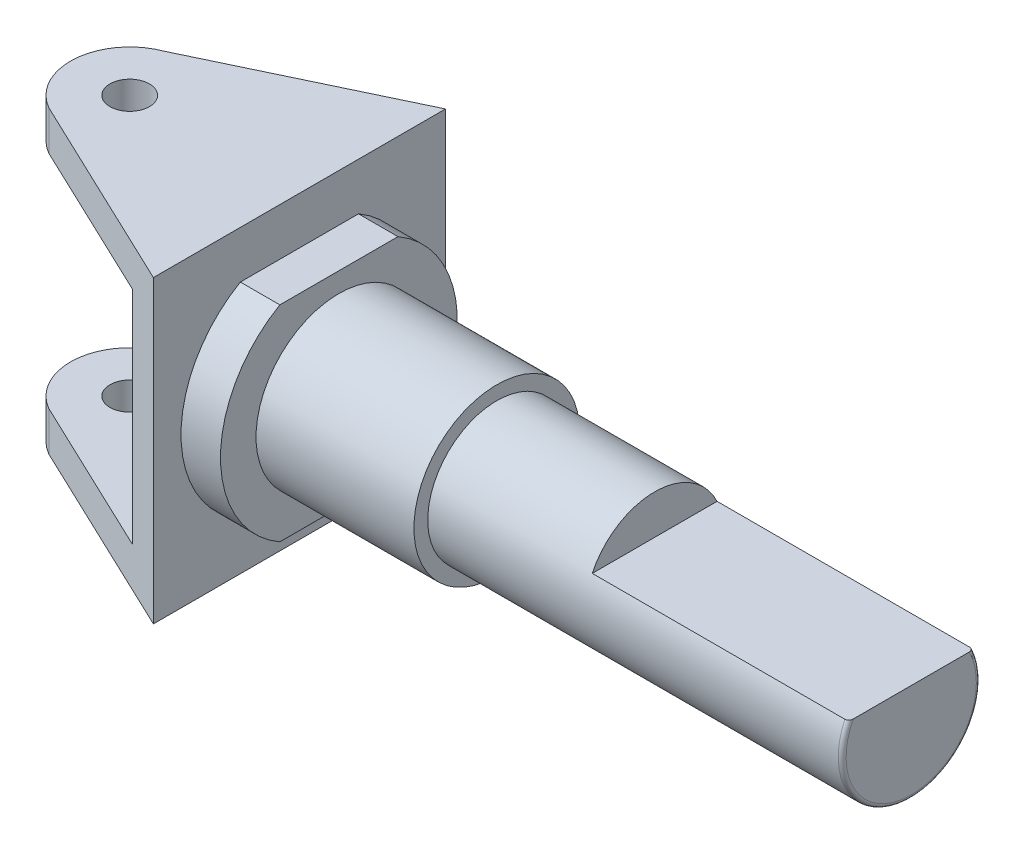
SolidWorks part; units mm, degrees
ref_plane "Front Plane" through (0, 0, 0) normal (0, 0, 1) x (1, 0, 0)
ref_plane "Top Plane" through (0, 0, 0) normal (0, 1, 0) x (1, 0, 0)
ref_plane "Right Plane" through (0, 0, 0) normal (1, 0, 0) x (0, 0, -1)
sketch "Sketch1" plane through (0, 0, 0) normal (0, 0, 1) x (1, 0, 0)
  line L0 (-61.9499, 30.1039) -> (-61.9499, 20.1039)
  line L5 (-61.9499, 30.1039) -> (-3.9499, 30.1039)
  line L6 (-3.9499, 30.1039) -> (-3.9499, -45.8961)
  line L7 (-3.9499, -45.8961) -> (-61.9499, -45.8961)
  line L8 (-61.9499, -45.8961) -> (-61.9499, -35.8961)
  line L9 (-61.9499, -35.8961) -> (-13.9499, -35.8961)
  line L10 (-13.9499, -35.8961) -> (-13.9499, 20.1039)
  line L11 (-61.9499, 20.1039) -> (-13.9499, 20.1039)
extrude "Boss-Extrude1" add sketch "Sketch1" along normal blind 74
sketch "Sketch2" plane through (0, 30.1039, 0) normal (0, 1, 0) x (1, 0, 0)
  line L0 (-3.9499, -74) -> (-54.4721, -49.9775)
  line L2 (-3.9499, 0) -> (-52.2674, -22.9741)
  line L4 (-3.9499, 0) -> (-61.9499, 0)
  line L5 (-61.9499, 0) -> (-61.9499, -37)
  line L6 (-3.9499, -74) -> (-61.9499, -74)
  line L7 (-61.9499, -74) -> (-61.9499, -37)
  arc A1 (-52.2674, -22.9741) -> (-54.4721, -49.9775) centre (-46.9499, -37) ccw
  line M2 (-3.9499, 0) -> (-61.9499, 0)
  line M3 (-61.9499, 0) -> (-61.9499, -74)
  line M4 (-61.9499, -74) -> (-3.9499, -74)
extrude "Cut-Extrude1" cut sketch "Sketch2" against normal blind 100 contours A1 L2 M2 M3 | A1 L0 M3 M4 region at (-42.9391, 30.1039, 64.4486) region at (-42.9381, 30.1039, 9.55)
sketch "Sketch3" plane through (0, 30.1039, 0) normal (0, 1, 0) x (1, 0, 0)
  circle A0 centre (-46.9499, -37) radius 5
extrude "Cut-Extrude2" cut sketch "Sketch3" against normal blind 100
sketch3d "3DSketch4"
  line L0 (-8.9499, 30.1039, 74) -> (-8.9499, -7.8961, 74) construction
  line L1 (-8.9499, -7.8961, 74) -> (-8.9499, -7.8961, 0) construction
  circle A0 centre (-8.9499, -7.8961, 37) radius 30
  point P5 (21.0501, -7.8961, 37)
  dimension "D1" = 5
extrude "Boss-Extrude2" add sketch "3DSketch4" along direction (1, 0, 0) on the side of the normal blind 15
sketch3d "3DSketch5"
  line L0 (1.0501, 30.1039, 74) -> (1.0501, -45.8961, 74) construction
  line L1 (1.0501, -7.8961, 74) -> (1.0501, -7.8961, 0) construction
  circle A4 centre (1.0501, -7.8961, 37) radius 21
  point P2 (22.0501, -7.8961, 37)
  dimension "D2" = 42
  dimension "D1" = 5
extrude "Boss-Extrude3" add sketch "3DSketch5" along direction (1, 0, 0) on the side of the normal blind 45
sketch3d "3DSketch6"
  line L0 (41.0501, -45.8961, 74) -> (41.0501, -7.8961, 74) construction
  line L1 (41.0501, -7.8961, 74) -> (41.0501, -7.8961, 0) construction
  circle A0 centre (41.0501, -7.8961, 37) radius 17.5
  point P6 (58.5501, -7.8961, 37)
  dimension "D1" = 5
extrude "Boss-Extrude4" add sketch "3DSketch6" along direction (1, 0, 0) on the side of the normal blind 110
fillet "Fillet1" radius 1 1 edges at (151.0501, -7.8961, 19.5)
sketch "Sketch4" plane through (151.0501, 0, 0) normal (1, 0, 0) x (0, 0, -1)
  line L1 (-52.8114, -0.3961) -> (-21.1886, -0.3961) construction
  line L2 (-52.8114, -0.3961) -> (-21.1886, -0.3961)
  arc A1 (-21.1886, -0.3961) -> (-52.8114, -0.3961) centre (-37, -7.8961) ccw
extrude "Cut-Extrude3" cut sketch "Sketch4" against normal blind 65
sketch "Sketch5" plane through (6.0501, 0, 0) normal (1, 0, 0) x (0, 0, -1)
  line L0 (-37, -7.8961) -> (-37, 18.1039) construction
  line L3 (-37, -7.8961) -> (-37, -33.8961) construction
  line L4 (-37, 18.1039) -> (-22.0334, 18.1039) construction
  line L5 (-22.0334, 18.1039) -> (-51.9666, 18.1039)
  line L6 (-37, -33.8961) -> (-51.9666, -33.8961) construction
  line L7 (-51.9666, -33.8961) -> (-22.0334, -33.8961)
  arc A0 (-51.9666, -33.8961) -> (-22.0334, -33.8961) centre (-37, -7.8961) ccw
  arc A1 (-22.0334, 18.1039) -> (-51.9666, 18.1039) centre (-37, -7.8961) ccw
  circle A2 centre (-37, -7.8961) radius 30 construction
  circle A3 centre (-37, -7.8961) radius 30 construction
extrude "Cut-Extrude4" cut sketch "Sketch5" against normal blind 10 contours A1 L5 | A0 L7
